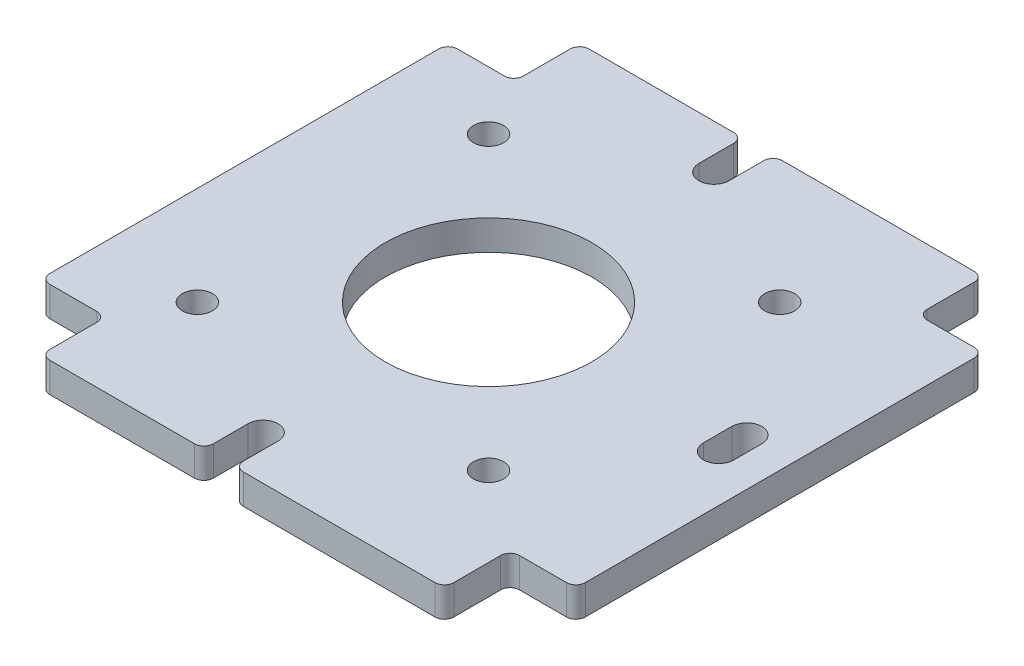
SolidWorks part; units mm, degrees
material "AISI 1045 Steel, cold drawn"
ref_plane "Front Plane" through (0, 0, 0) normal (0, 0, 1) x (1, 0, 0)
ref_plane "Top Plane" through (0, 0, 0) normal (0, 1, 0) x (1, 0, 0)
ref_plane "Right Plane" through (0, 0, 0) normal (1, 0, 0) x (0, 0, -1)
sketch "Sketch1" plane through (0, 0, 0) normal (0, 1, 0) x (1, 0, 0)
  line L1 (15.5, -15.5) -> (-15.5, -15.5) construction
  line L2 (15.5, -15.5) -> (15.5, 15.5) construction
  line L3 (15.5, 15.5) -> (-15.5, 15.5) construction
  line L4 (-15.5, -15.5) -> (-15.5, 15.5) construction
  line L5 (15.5, -15.5) -> (-15.5, 15.5) construction
  line L6 (15.5, 15.5) -> (-15.5, -15.5) construction
  line L7 (21, -21) -> (-21, -21)
  line L8 (21, -21) -> (21, 21)
  line L9 (21, 21) -> (-21, 21)
  line L10 (-21, -21) -> (-21, 21)
  line L11 (21, -21) -> (-21, 21) construction
  line L12 (21, 21) -> (-21, -21) construction
  circle A0 centre (0, 0) radius 11
  dimension "D1" = 22
  dimension "D2" = 31
  dimension "D3" = 42
extrude "Boss-Extrude1" add sketch "Sketch1" along normal mid plane 3.175
hole_wizard "M3 Clearance Hole1" positions "Sketch2" profile "Sketch3" hole size "M3" standard "ANSI Metric" end condition through all
sketch "Sketch2" plane through (0, 1.5875, 0) normal (0, 1, 0) x (1, 0, 0)
  point P0 (-15.5, 15.5)
  point P3 (15.5, 15.5)
  point P6 (15.5, -15.5)
  point P9 (-15.5, -15.5)
sketch "Sketch3" plane through (-15.5, 1.5875, -15.5) normal (1, 0, 0) x (0, 0, 1)
  line L0 (0, 0) -> (0, 3.175)
  line L1 (0, 3.175) -> (1.6, 3.175)
  line L2 (1.6, 3.175) -> (1.6, 0)
  line L5 (1.6, 0) -> (0, 0)
  line L11 (0, -6.35) -> (0, 107.95) construction
  dimension "Thru Hole Dia." = 3.2
  dimension "Thru Hole Depth" = 3.175
sketch "Sketch4" plane through (0, 1.5875, 0) normal (0, 1, 0) x (1, 0, 0)
  line L0 (0, -24) -> (0, -29) construction
  line L1 (1.6, -24) -> (1.6, -28.7)
  line L2 (-1.6, -24) -> (-1.6, -28.7)
  line L3 (26, 1.5) -> (26, -1.5) construction
  line L4 (27.6, 1.5) -> (27.6, -1.5)
  line L5 (24.4, 1.5) -> (24.4, -1.5)
  line L6 (-19, -21) -> (14, -21)
  line L9 (-21, -21) -> (21, -21) construction
  line L10 (-21, 21) -> (-26, 21)
  line L11 (21, -21) -> (21, 21) construction
  line L12 (21, 0) -> (-21, 0) construction
  line L13 (0, 24) -> (0, 29) construction
  line L14 (1.6, 28.7) -> (14, 28.7)
  line L15 (-19, -21) -> (-19, -28.7)
  line L16 (-19, -28.7) -> (-1.6, -28.7)
  line L17 (14, -28.7) -> (14, -21)
  line L18 (-21, 21) -> (-21, -21) construction
  line L19 (1.6, -28.7) -> (14, -28.7)
  line L20 (14, 28.7) -> (14, 21)
  line L21 (-19, 28.7) -> (-1.6, 28.7)
  line L22 (-19, 21) -> (-19, 28.7)
  line L23 (-19, 21) -> (14, 21)
  line L24 (-1.6, 24) -> (-1.6, 28.7)
  line L25 (1.6, 24) -> (1.6, 28.7)
  line L26 (21, 14) -> (31, 14)
  line L27 (31, 14) -> (31, -14)
  line L28 (31, -14) -> (21, -14)
  line L29 (21, 21) -> (-21, 21) construction
  line L30 (21, 14) -> (21, -14)
  line L31 (-26, 21) -> (-26, -21)
  line L32 (-26, -21) -> (-21, -21)
  line L33 (-21, 21) -> (-21, -21)
  arc A0 (1.6, -24) -> (-1.6, -24) centre (0, -24) ccw
  arc A2 (27.6, 1.5) -> (24.4, 1.5) centre (26, 1.5) ccw
  arc A3 (24.4, -1.5) -> (27.6, -1.5) centre (26, -1.5) ccw
  arc A6 (1.6, 24) -> (-1.6, 24) centre (0, 24) cw
  point P10 (26, 0)
  point P17 (0, 0)
  dimension "D1" = 1.6
  dimension "D12" = 1.6
  dimension "D2" = 3
  dimension "D3" = 5
  dimension "D4" = 10
  dimension "D5" = 5
  dimension "D6" = 7.7
  dimension "D7" = 7
  dimension "D8" = 7
  dimension "D9" = 7
  dimension "D10" = 7
  dimension "D11" = 3
  dimension "D13" = 5
extrude "Boss-Extrude2" add sketch "Sketch4" against normal up to vertex (3.175 mm away) up to point (21, -1.5875, -21)
sketch "Sketch5" plane through (0, 1.5875, 0) normal (0, 1, 0) x (1, 0, 0)
  line L0 (21, -14) -> (31, -14) construction
  line L17 (31, 14) -> (21, 14)
  line L18 (31, 14) -> (31, 21)
  line L19 (31, 21) -> (21, 21)
  line L20 (21, 14) -> (21, 21)
  line L21 (14, 28.7) -> (24, 28.7)
  line L22 (14, 28.7) -> (14, 21)
  line L23 (14, 21) -> (24, 21)
  line L24 (24, 28.7) -> (24, 21)
  line L25 (31, -14) -> (21, -14)
  line L26 (31, -14) -> (31, -21)
  line L27 (31, -21) -> (21, -21)
  line L28 (21, -14) -> (21, -21)
  line L29 (31, -14) -> (31, 14) construction
  line L30 (-19, -21) -> (-19, -28.7) construction
  line L31 (14, -28.7) -> (24, -28.7)
  line L32 (14, -28.7) -> (14, -21)
  line L33 (14, -21) -> (24, -21)
  line L34 (24, -28.7) -> (24, -21)
  line L35 (-26, -21) -> (-19, -21)
  line L36 (-26, -21) -> (-26, -21.7)
  line L37 (-26, -21.7) -> (-19, -21.7)
  line L38 (-19, -21) -> (-19, -21.7)
  line L39 (-19, 28.7) -> (-19, 21) construction
  line L40 (-26, 21) -> (-19, 21)
  line L41 (-26, 21) -> (-26, 21.7)
  line L42 (-26, 21.7) -> (-19, 21.7)
  line L43 (-19, 21) -> (-19, 21.7)
  line L44 (-1.6, 28.7) -> (-19, 28.7) construction
  line L45 (31, 21) -> (24, 21)
  line L46 (31, 21) -> (31, 21.7)
  line L47 (31, 21.7) -> (24, 21.7)
  line L48 (24, 21) -> (24, 21.7)
  line L49 (31, -21) -> (24, -21)
  line L50 (31, -21) -> (31, -21.7)
  line L51 (31, -21.7) -> (24, -21.7)
  line L52 (24, -21) -> (24, -21.7)
  line L53 (-19, -28.7) -> (-1.6, -28.7) construction
  line L54 (-26, 21) -> (-26, -21) construction
  line L55 (-19, 21) -> (-26, 21) construction
  point P47 (-24, -21)
  point P49 (-24, 21)
  circle M1 centre (-15.5, 15.5) radius 1.6
  circle M2 centre (15.5, 15.5) radius 1.6
  circle M3 centre (15.5, -15.5) radius 1.6
  circle M4 centre (-15.5, -15.5) radius 1.6
  line M6 (-26, -21) -> (-19, -21)
  line M7 (-19, -21) -> (-19, -28.7)
  line M8 (-19, -28.7) -> (-1.6, -28.7)
  line M9 (-1.6, -28.7) -> (-1.6, -24)
  arc M10 (-1.6, -24) -> (1.6, -24) centre (0, -24) cw
  line M11 (1.6, -24) -> (1.6, -28.7)
  line M12 (1.6, -28.7) -> (14, -28.7)
  line M13 (14, -28.7) -> (14, -21)
  line M14 (14, -21) -> (21, -21)
  line M15 (21, -21) -> (21, -14)
  line M16 (21, -14) -> (31, -14)
  line M17 (31, -14) -> (31, 14)
  line M18 (31, 14) -> (21, 14)
  line M19 (21, 14) -> (21, 21)
  line M20 (21, 21) -> (14, 21)
  line M21 (14, 21) -> (14, 28.7)
  line M22 (14, 28.7) -> (1.6, 28.7)
  line M23 (1.6, 28.7) -> (1.6, 24)
  arc M24 (1.6, 24) -> (-1.6, 24) centre (0, 24) cw
  line M25 (-1.6, 24) -> (-1.6, 28.7)
  line M26 (-1.6, 28.7) -> (-19, 28.7)
  line M27 (-19, 28.7) -> (-19, 21)
  line M28 (-19, 21) -> (-26, 21)
  circle M29 centre (0, 0) radius 11
  line M30 (24.4, -1.5) -> (24.4, 1.5)
  arc M31 (24.4, 1.5) -> (27.6, 1.5) centre (26, 1.5) cw
  line M32 (27.6, 1.5) -> (27.6, -1.5)
  arc M33 (27.6, -1.5) -> (24.4, -1.5) centre (26, -1.5) cw
  dimension "D1" = 7
  dimension "D2" = 7
  dimension "D3" = 7
extrude "Boss-Extrude3" add sketch "Sketch5" against normal up to surface (3.175 mm away) contours M28 M6 M7 M8 M9 M10 M11 M12 M13 M14 M15 M16 M17 M18 M19 M20 M21 M22 M23 M24 M25 M26 M27 M2 M4 M29 M33 M30 M31 M32 M3 M1 | M21 M20 | M19 M18 | L22 M16 M15 | L17 L20 M14 M13 | L36 L37 M7 M6 | L51 L50 L27 L34 | L46 L47 L24 L19 | L42 L41 M28 M27 region at (-22.5, 1.5875, -21.35) region at (26, 1.5875, -17.5) region at (-22.5, 1.5875, 21.35) region at (26, 1.5875, 17.5) region at (27.5, 1.5875, -21.35) region at (19, 1.5875, -24.85) region at (27.5, 1.5875, 21.35) region at (19, 1.5875, 24.85) up to face at (-15.5, -1.5875, -13.9)
fillet "Fillet1" radius 1 16 edges at (-1.6, 0, 28.7) (1.6, 0, 28.7) (-19, 0, 28.7) (1.6, 0, -28.7) (-1.6, 0, -28.7) (-19, 0, -28.7) (24, 0, -28.7) (24, 0, 28.7) (-26, 0, 21.7) (-19, 0, 21.7) (24, 0, 21.7) (31, 0, 21.7) (31, 0, -21.7) (24, 0, -21.7) (-19, 0, -21.7) (-26, 0, -21.7)
